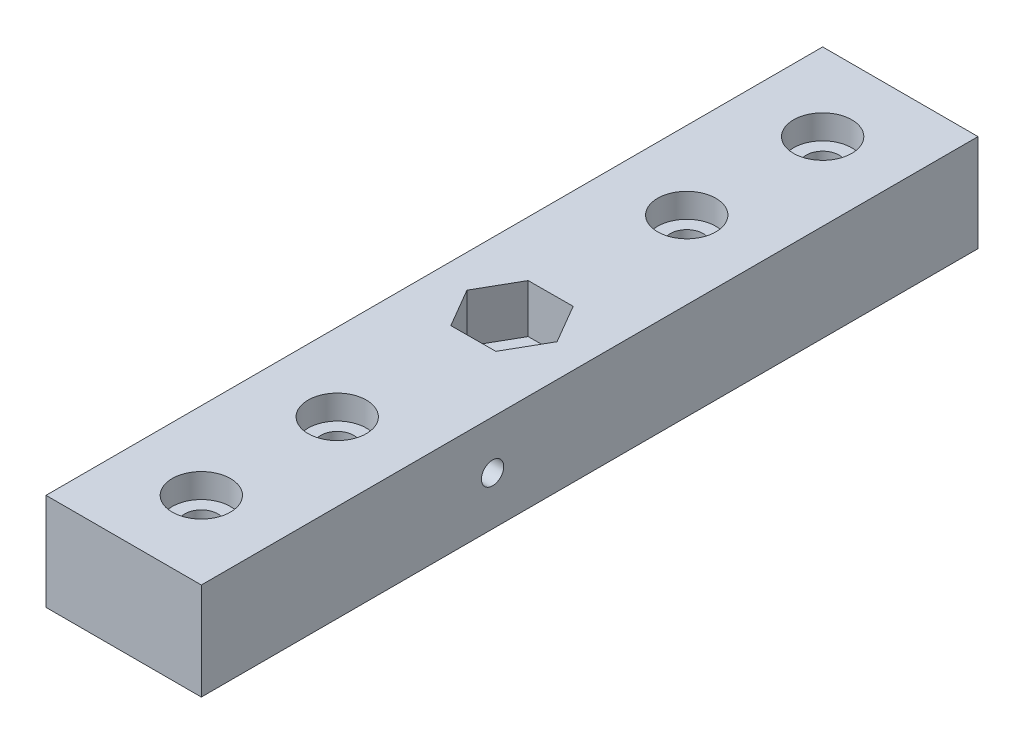
SolidWorks part; units mm, degrees
ref_plane "Ebene vorne" through (0, 0, 0) normal (0, 0, 1) x (1, 0, 0)
ref_plane "Ebene oben" through (0, 0, 0) normal (0, 1, 0) x (1, 0, 0)
ref_plane "Ebene rechts" through (0, 0, 0) normal (1, 0, 0) x (0, 0, -1)
sketch "Sketch1" plane through (0, 0, 0) normal (0, 1, 0) x (1, 0, 0)
  line L0 (0, 88.4363) -> (0, -16.8125) construction
  line L1 (-8, 80) -> (8, 80)
  line L2 (-8, 80) -> (-8, 0)
  line L3 (-8, 0) -> (8, 0)
  line L4 (8, 80) -> (8, 0)
  dimension "D1" = 16
  dimension "D2" = 80
sketch "Sketch2" plane through (0, 0, 0) normal (0, 1, 0) x (1, 0, 0)
  line L0 (0, 87.0713) -> (0, -18.1775) construction
  circle A0 centre (0, 72) radius 2.35
  circle A1 centre (0, 58) radius 2.35
  circle A2 centre (0, 22) radius 2.35
  circle A3 centre (0, 8) radius 2.35
  circle A4 centre (0, 72) radius 3
  circle A5 centre (0, 58) radius 3
  circle A6 centre (0, 22) radius 3
  circle A7 centre (0, 8) radius 3
  circle A8 centre (0, 72) radius 1.7
  circle A9 centre (0, 58) radius 1.7
  circle A10 centre (0, 22) radius 1.7
  circle A11 centre (0, 8) radius 1.7
  dimension "D3" = 4.7
  dimension "D1" = 6
  dimension "D2" = 3.4
  dimension "D4" = 14
  dimension "D5" = 14
  dimension "D6" = 50
  dimension "D7" = 8
extrude "Boss-Extrude1" add sketch "Sketch1" along normal blind 10
extrude "Cut-Extrude1" cut sketch "Sketch2" along normal blind 2.5 contours A0 | A1 | A2 | A3
extrude "Cut-Extrude2" cut sketch "Sketch2<3>" along normal through all contours A8 | A9 | A10 | A11
sketch "Sketch2<3>" plane through (0, 0, 0) normal (0, 1, 0) x (1, 0, 0) same geometry as "Sketch2"
extrude "Cut-Extrude3" cut sketch "Sketch2<4>" along normal through all from offset 7.5 contours A4 | A5 | A6 | A7
sketch "Sketch2<4>" plane through (0, 0, 0) normal (0, 1, 0) x (1, 0, 0) same geometry as "Sketch2"
sketch "Sketch3" plane through (8, 0, 0) normal (1, 0, 0) x (0, 0, -1)
  circle A0 centre (30, 5) radius 1.15
  dimension "D1" = 2.3
  dimension "D2" = 5
  dimension "D3" = 30
extrude "Cut-Extrude4" cut sketch "Sketch3" against normal through all
sketch "Sketch4" plane through (0, 10, 0) normal (0, -1, 0) x (1, 0, 0)
  line L0 (0, 0) -> (0, -80) construction
  line L1 (8, -80) -> (-8, -80) construction
  line L3 (2.2916, -44.0102) -> (4.6188, -40.0206)
  line L4 (4.6188, -40.0206) -> (2.3272, -36.0103)
  line L5 (2.3272, -36.0103) -> (-2.2916, -35.9898)
  line L6 (-2.2916, -35.9898) -> (-4.6188, -39.9794)
  line L7 (-4.6188, -39.9794) -> (-2.3272, -43.9897)
  line L8 (-2.3272, -43.9897) -> (2.2916, -44.0102)
  circle A0 centre (0, -40) radius 4 construction
  dimension "D1" = 8
extrude "Cut-Extrude5" cut sketch "Sketch4" along normal blind 5
sketch "Sketch6" plane through (0, 10, 0) normal (0, -1, 0) x (-1, 0, 0)
  circle A0 centre (0, 40) radius 2.5
  dimension "D1" = 5
extrude "Cut-Extrude6" cut sketch "Sketch6" along normal blind 25
